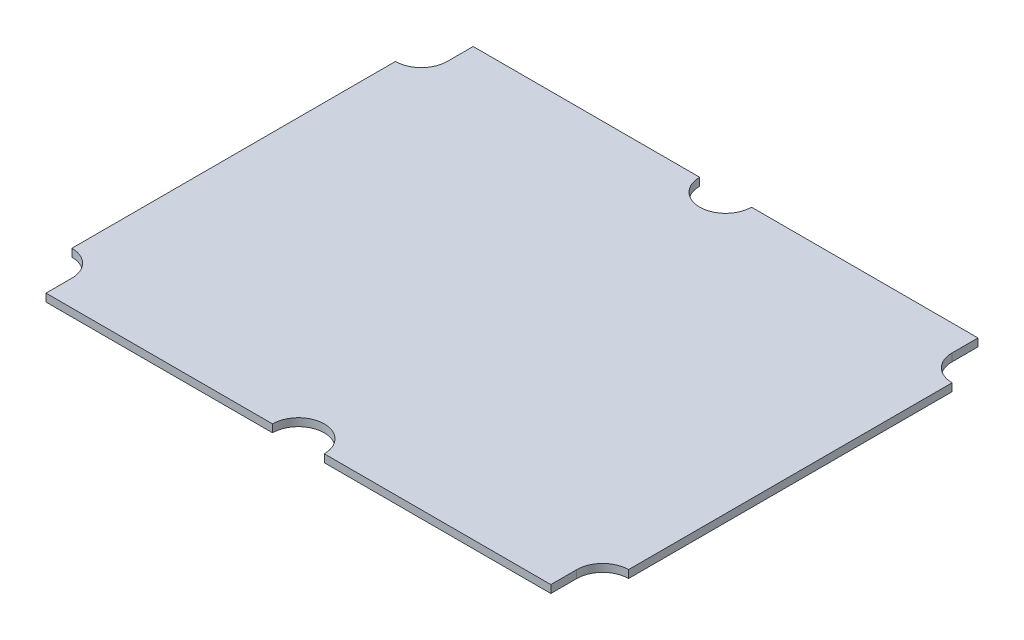
SolidWorks part; units mm, degrees
ref_plane "Płaszczyzna przednia" through (0, 0, 0) normal (0, 0, 1) x (1, 0, 0)
ref_plane "Płaszczyzna górna" through (0, 0, 0) normal (0, 1, 0) x (1, 0, 0)
ref_plane "Płaszczyzna prawa" through (0, 0, 0) normal (1, 0, 0) x (0, 0, -1)
sketch "Sketch1" plane through (0, 0, 0) normal (0, 1, 0) x (1, 0, 0)
  line L0 (102.5, -67.5) -> (102.5, 57.5)
  line L5 (92.5, -87.5) -> (5, -87.5)
  line L7 (92.5, 77.5) -> (5, 77.5)
  line L9 (-102.5, 67.5) -> (-102.5, 77.5)
  line L10 (-15, -87.5) -> (-102.5, -87.5)
  line L11 (-112.5, -67.5) -> (-112.5, 57.5)
  line L13 (92.5, 67.5) -> (92.5, 77.5)
  line L14 (92.5, -77.5) -> (92.5, -87.5)
  line L15 (-102.5, -77.5) -> (-102.5, -87.5)
  line L17 (-15, 77.5) -> (-102.5, 77.5)
  arc A0 (-112.5, 57.5) -> (-102.5, 67.5) centre (-112.5, 67.5) ccw
  arc A1 (-102.5, -77.5) -> (-112.5, -67.5) centre (-112.5, -77.5) ccw
  arc A2 (102.5, -67.5) -> (92.5, -77.5) centre (102.5, -77.5) ccw
  arc A3 (92.5, 67.5) -> (102.5, 57.5) centre (102.5, 67.5) ccw
  arc A4 (5, -87.5) -> (-15, -87.5) centre (-5, -87.5) ccw
  arc A5 (-15, 77.5) -> (5, 77.5) centre (-5, 77.5) ccw
extrude "Boss-Extrude3" add sketch "Sketch1" along normal blind 3
